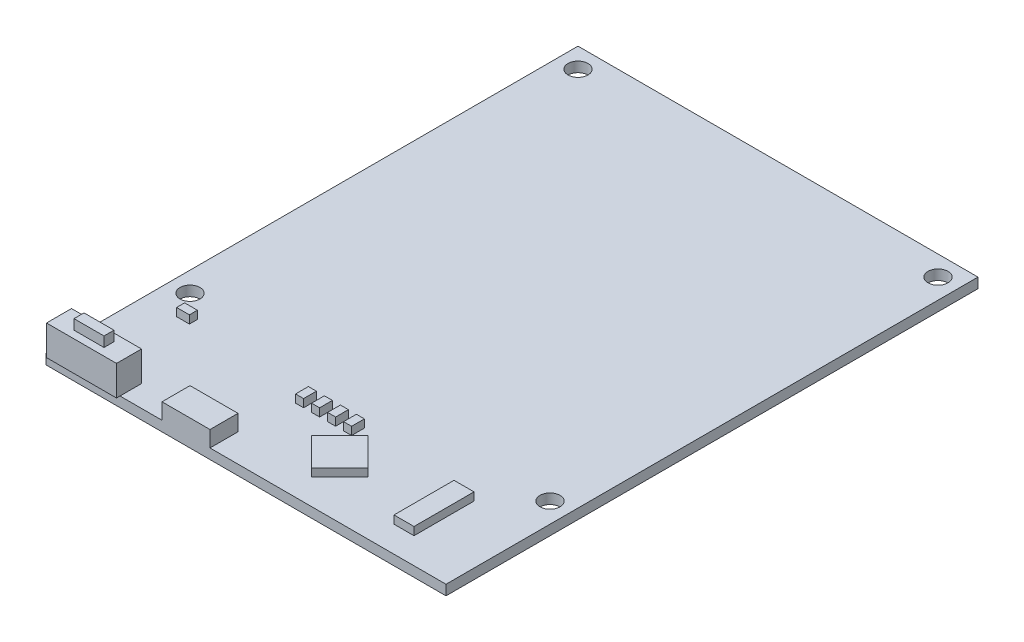
SolidWorks part; units mm, degrees
ref_plane "Front Plane" through (0, 0, 0) normal (0, 0, 1) x (1, 0, 0)
ref_plane "Top Plane" through (0, 0, 0) normal (0, 1, 0) x (1, 0, 0)
ref_plane "Right Plane" through (0, 0, 0) normal (1, 0, 0) x (0, 0, -1)
sketch "Sketch1" plane through (0, 0, 0) normal (0, 1, 0) x (1, 0, 0)
  line L1 (-31.75, -42.2275) -> (31.75, -42.2275)
  line L2 (-31.75, -42.2275) -> (-31.75, 42.2275)
  line L3 (-31.75, 42.2275) -> (31.75, 42.2275)
  line L4 (31.75, -42.2275) -> (31.75, 42.2275)
  line L5 (-31.75, -42.2275) -> (31.75, 42.2275) construction
  line L6 (-31.75, 42.2275) -> (31.75, -42.2275) construction
  circle A0 centre (-28.575, 39.0525) radius 1.5875
  circle A1 centre (28.575, 39.0525) radius 1.5875
  circle A2 centre (-28.575, -22.5425) radius 1.5875
  circle A3 centre (28.575, -22.5425) radius 1.5875
  point P0 (0, 0)
  dimension "D3" = 3.175
  dimension "D4" = 3.175
  dimension "D5" = 3.175
  dimension "D8" = 61.595
  dimension "D9" = 57.15
  dimension "D1" = 63.5
  dimension "D2" = 84.455
  dimension "D6" = 2
  dimension "D7" = 2
extrude "Boss-Extrude1" add sketch "Sketch1" along normal blind 1.6
sketch "Sketch2" plane through (0, 1.6, 0) normal (0, 1, 0) x (1, 0, 0)
  line L0 (-31.75, -42.2275) -> (31.75, -42.2275) construction
  line L1 (6.35, -29.2284) -> (10.8401, -33.7185)
  line L2 (6.35, -29.2284) -> (1.8599, -33.7185)
  line L3 (1.8599, -33.7185) -> (6.35, -38.2086)
  line L4 (10.8401, -33.7185) -> (6.35, -38.2086)
  line L5 (6.35, -29.2284) -> (6.35, -38.2086) construction
  line L6 (1.8599, -33.7185) -> (10.8401, -33.7185) construction
  line L8 (-31.75, 42.2275) -> (-31.75, -42.2275) construction
  line L9 (-2.54, -27.2415) -> (-2.54, -29.2735)
  line L10 (-5.08, -27.2415) -> (-3.81, -27.2415)
  line L11 (-5.08, -27.2415) -> (-5.08, -29.2735)
  line L12 (-5.08, -29.2735) -> (-3.81, -29.2735)
  line L13 (-3.81, -27.2415) -> (-3.81, -29.2735)
  line L14 (-5.08, -27.2415) -> (-3.81, -29.2735) construction
  line L15 (-5.08, -29.2735) -> (-3.81, -27.2415) construction
  line L16 (-2.54, -27.2415) -> (-1.27, -27.2415)
  line L17 (-2.54, -29.2735) -> (-1.27, -29.2735)
  line L18 (-1.27, -27.2415) -> (-1.27, -29.2735)
  line L19 (0, -27.2415) -> (0, -29.2735)
  line L20 (0, -27.2415) -> (1.27, -27.2415)
  line L21 (0, -29.2735) -> (1.27, -29.2735)
  line L22 (1.27, -27.2415) -> (1.27, -29.2735)
  line L23 (2.54, -27.2415) -> (2.54, -29.2735)
  line L24 (2.54, -27.2415) -> (3.81, -27.2415)
  line L25 (2.54, -29.2735) -> (3.81, -29.2735)
  line L26 (3.81, -27.2415) -> (3.81, -29.2735)
  line L28 (19.3675, -28.575) -> (22.5425, -28.575)
  line L29 (19.3675, -28.575) -> (19.3675, -38.1)
  line L30 (19.3675, -38.1) -> (22.5425, -38.1)
  line L31 (22.5425, -28.575) -> (22.5425, -38.1)
  line L32 (19.3675, -28.575) -> (22.5425, -38.1) construction
  line L33 (19.3675, -38.1) -> (22.5425, -28.575) construction
  line L34 (-26.416, -26.8288) -> (-24.384, -26.8288)
  line L35 (-26.416, -26.8288) -> (-26.416, -25.5587)
  line L36 (-26.416, -25.5587) -> (-24.384, -25.5587)
  line L37 (-24.384, -26.8288) -> (-24.384, -25.5587)
  line L38 (-26.416, -26.8288) -> (-24.384, -25.5587) construction
  line L39 (-26.416, -25.5587) -> (-24.384, -26.8288) construction
  point P0 (6.35, -33.7185)
  point P9 (-4.445, -28.2575)
  point P14 (20.955, -33.3375)
  point P31 (-25.4, -26.1938)
  dimension "D1" = 6.35
  dimension "D2" = 45
  dimension "D3" = 38.1
  dimension "D4" = 8.509
  dimension "D5" = 1.27
  dimension "D6" = 2.032
  dimension "D7" = 27.305
  dimension "D8" = 13.97
  dimension "D10" = 2.54
  dimension "D11" = 3.175
  dimension "D12" = 9.525
  dimension "D13" = 8.89
  dimension "D14" = 52.705
  dimension "D15" = 1.27
  dimension "D16" = 2.032
  dimension "D17" = 6.35
  dimension "D18" = 16.0337
  dimension "D9" = 4
extrude "Boss-Extrude2" add sketch "Sketch2" along normal blind 1.27
sketch "Sketch3" plane through (0, 1.6, 0) normal (0, 1, 0) x (1, 0, 0)
  line L0 (-31.75, -42.2275) -> (31.75, -42.2275) construction
  line L1 (-13.335, -37.7825) -> (-5.715, -37.7825)
  line L2 (-13.335, -37.7825) -> (-13.335, -42.2275)
  line L3 (-13.335, -42.2275) -> (-5.715, -42.2275)
  line L4 (-5.715, -37.7825) -> (-5.715, -42.2275)
  line L5 (-13.335, -37.7825) -> (-5.715, -42.2275) construction
  line L6 (-13.335, -42.2275) -> (-5.715, -37.7825) construction
  line L7 (-31.75, 42.2275) -> (-31.75, -42.2275) construction
  point P0 (-9.525, -40.005)
  dimension "D1" = 4.445
  dimension "D2" = 7.62
  dimension "D3" = 2.2225
  dimension "D4" = 22.225
extrude "Boss-Extrude3" add sketch "Sketch3" along normal blind 2.54
sketch "Sketch4" plane through (0, 0, 42.2275) normal (0, 0, 1) x (1, 0, 0)
  line L0 (-31.75, 1.6) -> (-13.335, 1.6) construction
  line L1 (-31.115, 6.3625) -> (-20.0025, 6.3625)
  line L2 (-31.115, 6.3625) -> (-31.115, 1.6)
  line L3 (-31.115, 1.6) -> (-20.0025, 1.6)
  line L4 (-20.0025, 6.3625) -> (-20.0025, 1.6)
  line L5 (-31.115, 6.3625) -> (-20.0025, 1.6) construction
  line L6 (-31.115, 1.6) -> (-20.0025, 6.3625) construction
  line L7 (-31.75, 1.6) -> (-31.75, 0) construction
  line L8 (-27.94, 6.3625) -> (-27.94, 7.95)
  line L9 (-27.94, 7.95) -> (-23.1775, 7.95)
  line L10 (-23.1775, 7.95) -> (-23.1775, 6.3625)
  point P0 (-25.5588, 3.9813)
  line M7 (-13.335, 1.6) -> (-31.75, 1.6)
  dimension "D1" = 11.1125
  dimension "D2" = 4.7625
  dimension "D3" = 6.1913
  dimension "D4" = 3.175
  dimension "D5" = 3.175
  dimension "D6" = 1.5875
extrude "Boss-Extrude4" add sketch "Sketch4" against normal blind 1.9844 and the other way blind 1.9844 from offset 1.4287 contours L10 L9 L8 L1 | L4 L1 L2 M7 region at (-25.5588, 3.9812, 42.2275) region at (-25.5588, 7.1562, 42.2275) offset against normal yes
sketch "Sketch5" plane through (0, 0, 42.7831) normal (0, 0, 1) x (1, 0, 0)
  line L1 (-27.94, 7.95) -> (-23.1775, 7.95)
  line L2 (-27.94, 7.95) -> (-27.94, 6.3625)
  line L3 (-27.94, 6.3625) -> (-23.1775, 6.3625)
  line L4 (-23.1775, 7.95) -> (-23.1775, 6.3625)
extrude "Cut-Extrude1" cut sketch "Sketch5" along normal up to next from offset 1.1906 offset against normal yes
extrude "Cut-Extrude2" cut sketch "Sketch5<2>" against normal up to next from offset 2.7781 offset against normal yes
sketch "Sketch5<2>" plane through (0, 0, 42.7831) normal (0, 0, 1) x (1, 0, 0) same geometry as "Sketch5"
